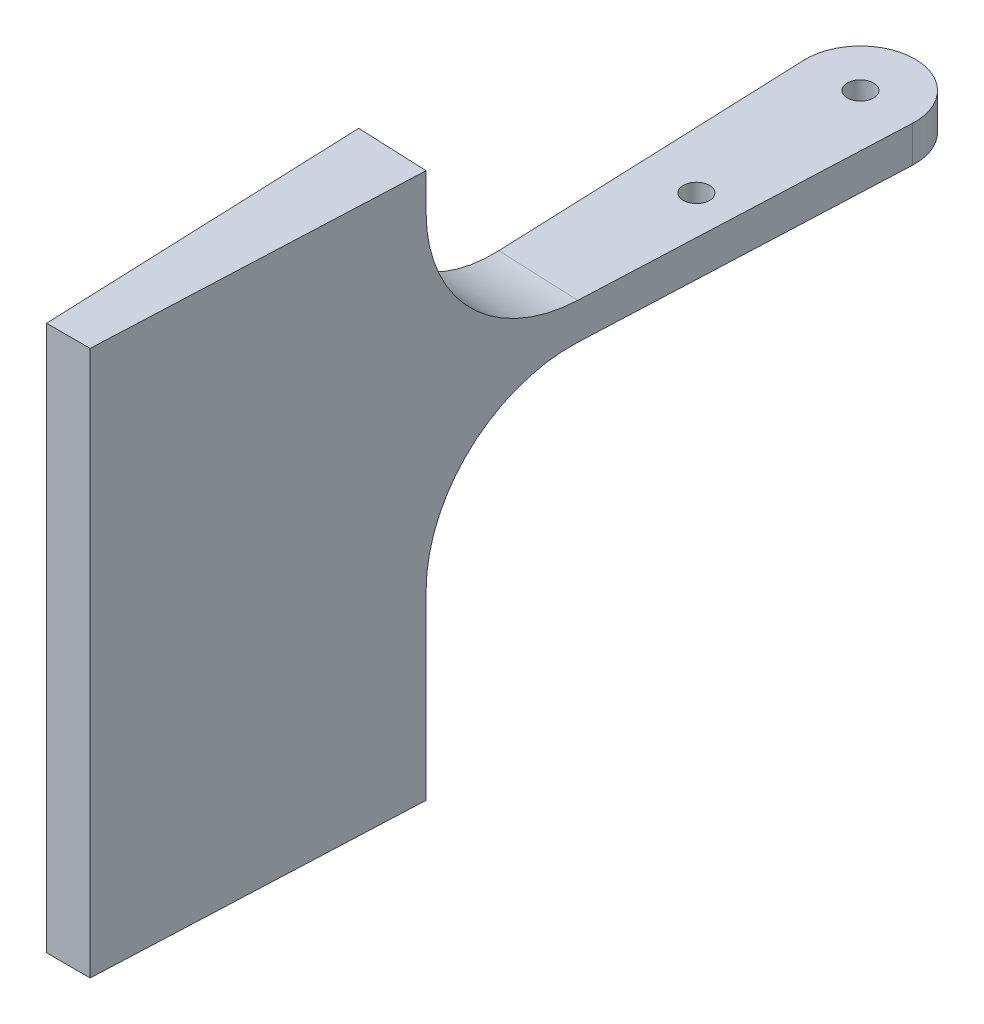
SolidWorks part; units mm, degrees
ref_plane "Front" through (0, 0, 0) normal (0, 0, 1) x (1, 0, 0)
ref_plane "Top" through (0, 0, 0) normal (0, 1, 0) x (1, 0, 0)
ref_plane "Right" through (0, 0, 0) normal (1, 0, 0) x (0, 0, -1)
sketch "Sketch1" plane through (0, 0, 0) normal (0, 1, 0) x (1, 0, 0)
  line L0 (-4.2443, -7.7934) -> (0, -116.2)
  line L1 (0, 0) -> (6, 0)
  line L2 (0, 0) -> (0, -116.2)
  line L3 (0, -116.2) -> (6, -116.2)
  line L4 (6, 0) -> (6, -116.2)
  line L5 (0, -116.2) -> (0, -14.2593)
  line L6 (0, -14.2593) -> (-4.2443, -7.7934)
  line L7 (10.7428, -7.8279) -> (6, -116.2)
  line L8 (6, -116.2) -> (6, -14.4776)
  line L9 (6, -14.4776) -> (10.7428, -7.8279)
  circle A0 centre (3.25, -7.5) radius 7.5
  point P11 (0, -114.2487)
  point P12 (6, -36.2348)
  point P14 (0, -36.2348)
  point P15 (6, -114.2446)
  dimension "D3" = 15
  dimension "D1" = 6
  dimension "D2" = 116.2
  dimension "D4" = 2.75
extrude "Boss-Extrude1" add sketch "Sketch1" along normal blind 5 contours L2 A0 L6 | L9 A0 L4 | L4 A0 L2 | A0 L0 L2 | A0 L4 L7 | A0 L2 L3 L4 | L9 A0 | L6 A0 | L9 L7 L8 region at (-1.3862, 0, 47.0132) region at (-1.6335, 0, 6.905) region at (-2.4835, 0, 11.2636) region at (2.999, 0, 65.495) region at (3.0144, 0, 7.5) region at (7.547, 0, 47.1607) region at (7.833, 0, 6.8624) region at (8.7681, 0, 11.4357)
sketch "Sketch2" plane through (0, 5, 0) normal (0, 1, 0) x (1, 0, 0)
  line L0 (-1.7499, -71.5034) -> (7.9376, -71.9274)
  line L1 (-4.2443, -7.7934) -> (0, -116.2) construction
  line L2 (10.7428, -7.8279) -> (6, -116.2) construction
  line L3 (7.9376, -71.9274) -> (6, -116.2)
  line L4 (6, -116.2) -> (0, -116.2)
  line L5 (0, -116.2) -> (-1.7499, -71.5034)
extrude "Boss-Extrude2" add sketch "Sketch2" along normal blind 25 and the other way blind 50
fillet "Fillet1" radius 20 2 edges at (3.0938, 0, 71.7154) (3.0938, 5, 71.7154)
sketch "Sketch3" plane through (0, 5, 0) normal (0, 1, 0) x (1, 0, 0)
  circle A0 centre (3.25, -7.5) radius 1.8
  circle A1 centre (4.1694, -30.982) radius 1.8
extrude "Cut-Extrude1" cut sketch "Sketch3" against normal blind 19
